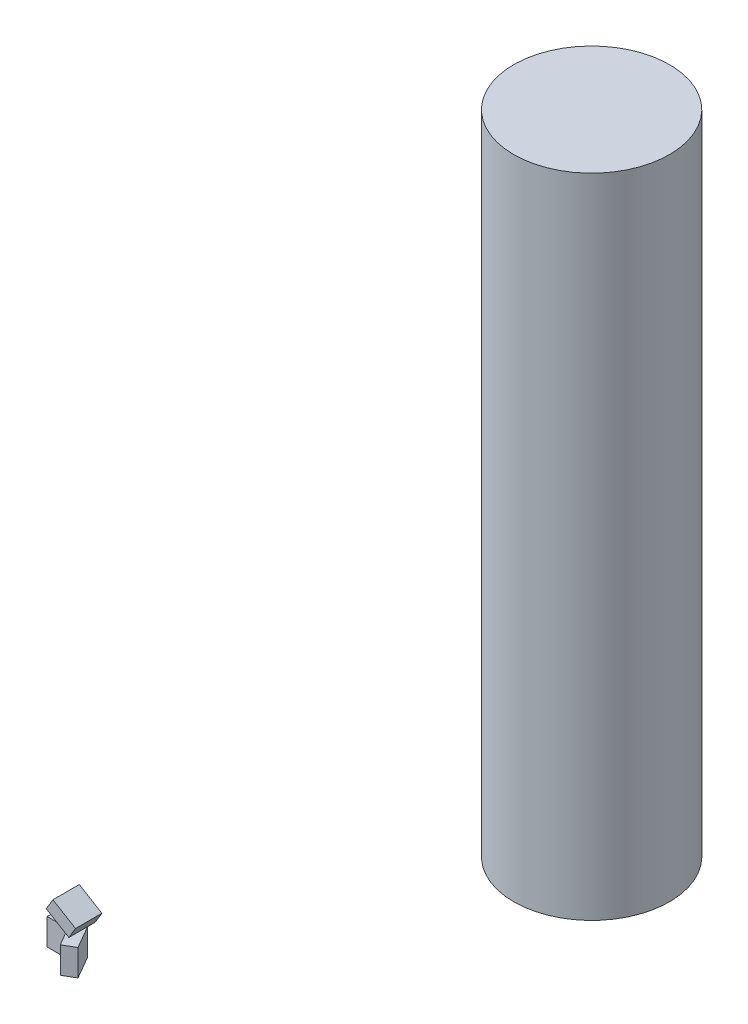
SolidWorks part; units mm, degrees
note: '?' marks a value the reader was unsure of.
ref_plane "Alzado" through (0, 0, 0) normal (0, 0, 1) x (1, 0, 0)
ref_plane "Planta" through (0, 0, 0) normal (0, 1, 0) x (1, 0, 0)
ref_plane "Vista lateral" through (0, 0, 0) normal (1, 0, 0) x (0, 0, -1)
sketch "Croquis1" plane through (0, 0, 0) normal (0, 1, 0) x (1, 0, 0)
  line L1 (300, 0) -> (-150, 259.8076)
  line L2 (-150, 259.8076) -> (-150, -259.8076)
  line L3 (-150, -259.8076) -> (300, 0)
  circle A0 centre (0, 0) radius 150 construction
  dimension "D1" = 300
surface "Superficie-Plano1" sketch "Croquis1"
sketch "Croquis4" plane through (0, 0, 0) normal (0, 1, 0) x (1, 0, 0)
  circle A0 centre (0, 10.6488) radius 60.1873
extrude "Saliente-Extruir1" add sketch "Croquis4" along normal blind 500
ref_plane "hith" through (0, 500, 0) normal (0, 1, 0) x (1, 0, 0)
ref_axis "Eje1" through (0, 0, 0) along (0, 1, 0)?
ref_plane "simetria" through (0, 250, 0) normal (0, 1, 0) x (1, 0, 0)
sketch "Croquis2" plane through (0, 500, 0) normal (0, 1, 0) x (1, 0, 0)
  line L1 (-300, 0) -> (150, -259.8076)
  line L2 (150, -259.8076) -> (150, 259.8076)
  line L3 (150, 259.8076) -> (-300, 0)
  circle A0 centre (0, 0) radius 150 construction
  dimension "D1" = 300
surface "Superficie-Plano2" sketch "Croquis2"
ref_axis "Eje6" through (-300, 500, 0) along (0.2572, -0.8575, 0.4456)?
ref_axis "Eje7" through (150, 500, 259.8076) along (-0.5145, -0.8575, 0)?
ref_axis "Eje8" through (-150, 0, 259.8076) along (0, 0, -1)?
ref_axis "Eje9" through (-151.8162, 0, 260.8562) along (0.866, 0, -0.5)?
ref_point "Punto1"
sketch "Croquis5" plane through (0, 0, 0) normal (0, 1, 0) x (1, 0, 0)
  line L0 (-139.8, -239.8076) -> (-139.8, -249.8076)
  line L1 (-139.8, -239.8076) -> (-160.2, -239.8076)
  line L2 (-160.2, -239.8076) -> (-160.2, -249.8076)
  line L6 (-150, -259.8076) -> (-150, 259.8076) construction
  line L11 (-160.2, -249.8076) -> (-139.8, -249.8076)
  point P4 (-150, -239.8076)
  point P13 (-150, -259.8076)
  dimension "D1" = 20.4
  dimension "D3" = 10
  dimension "D2" = 20
extrude "Saliente-Extruir2" add sketch "Croquis5" along normal mid plane 20.4 separate body
ref_plane "Plano3" through (-137.6147, 82.5688, 238.3556) normal (-0.4789, 0.2873, 0.8295) x (0.8779, 0.1568, 0.4525)
ref_plane "Plano4" through (-110.2941, 66.1765, 0) normal (-0.8575, 0.5145, 0) x (0, 0, 1)
sketch "Croquis8" plane through (-110.2941, 66.1765, 0) normal (-0.8575, 0.5145, 0) x (0, 0, 1)
  line L0 (249.6076, -32.1744) -> (270.0076, -32.1744)
  line L2 (270.0076, -32.1744) -> (270.0076, -42.1744)
  line L3 (270.0076, -42.1744) -> (249.6076, -42.1744)
  line L4 (249.6076, -42.1744) -> (249.6076, -32.1744)
  line L5 (259.8076, 505.9208) -> (259.8076, -77.1744) construction
  point P5 (259.8076, -32.1744)
  point P11 (259.8076, -77.1744)
  dimension "D1" = 20.4
  dimension "D3" = 10
  dimension "D2" = 45
extrude "Saliente-Extruir4" add sketch "Croquis8" along normal mid plane 20.4 separate body
ref_plane "Plano5" through (0, 0, 0) normal (0.866, 0, 0.5) x (0.5, 0, -0.866)
mirror "Simetría5" about plane through (0, 0, 0) normal (0.866, 0, 0.5) of "Saliente-Extruir4", "Saliente-Extruir2"
equation "\"printarea\" = 300"
equation "\"D1@Croquis1\"=\"printarea\""
equation "\"D1@Croquis2\"=\"printarea\""
equation "\"hitg\" = 500"
equation "\"D1@Saliente-Extruir1\"=\"hitg\""
equation "\"perfil\"= 20"
equation "\"clear\"= .4"
equation "\"D1@Croquis5\"= \"perfil\" + \"clear\""
equation "\"D1@Saliente-Extruir2\"=\"perfil\"+\"clear\""
equation "\"joind\" = 45"
equation "\"D1@Croquis8\"=\"perfil\"+\"clear\""
equation "\"D1@Saliente-Extruir4\"=\"perfil\"+\"clear\""
equation "\"D2@Croquis8\"=\"joind\""
equation "\"joind2\"= 20"
equation "\"D2@Croquis5\"=\"joind2\""
